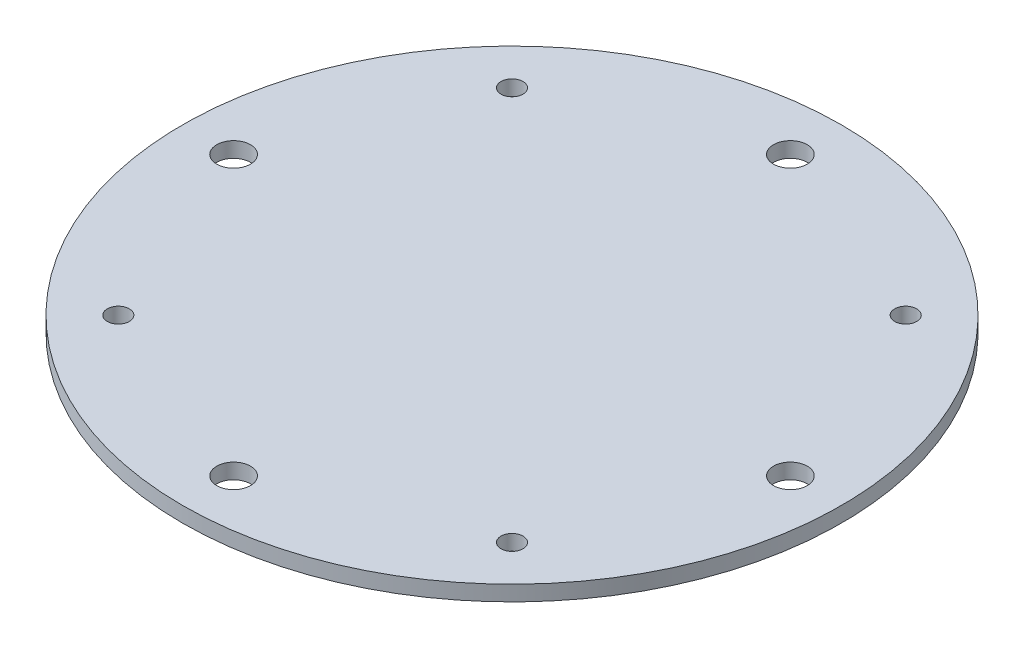
SolidWorks part; units mm, degrees
ref_plane "Front Plane" through (0, 0, 0) normal (0, 0, 1) x (1, 0, 0)
ref_plane "Top Plane" through (0, 0, 0) normal (0, 1, 0) x (1, 0, 0)
ref_plane "Right Plane" through (0, 0, 0) normal (1, 0, 0) x (0, 0, -1)
sketch "Sketch1" plane through (0, 0, 0) normal (0, 1, 0) x (1, 0, 0)
  circle A0 centre (0, 0) radius 64.4
  dimension "Diameter" = 128.8
extrude "Boss-Extrude1" add sketch "Sketch1" along normal mid plane 3
hole_wizard "M6 Clearance Hole1" positions "Sketch8" profile "Sketch9" hole size "M6" standard "ANSI Metric" end condition up to next
sketch "Sketch8" plane through (0, 1.5, 0) normal (0, 1, 0) x (1, 0, 0)
  line L0 (0, 0) -> (54.4, 0) construction
  point P0 (54.4, 0)
  dimension "ThreadedHoleDistance" = 54.4
sketch "Sketch9" plane through (54.4, 1.5, 0) normal (1, 0, 0) x (0, 0, 1)
  line L0 (0, 0) -> (0, 3)
  line L1 (0, 3) -> (3.3, 3)
  line L2 (3.3, 3) -> (3.3, 0)
  line L5 (3.3, 0) -> (0, 0)
  line L11 (0, -6.35) -> (0, 107.95) construction
  dimension "Thru Hole Dia." = 6.6
  dimension "Thru Hole Depth" = 3
pattern_circular "CirPattern2" count 4 over 360 about axis through (0, 1.5, 0) along (0, -1, 0) of "M6 Clearance Hole1" reverse direction yes
sketch "Sketch5" plane through (0, 1.5, 0) normal (0, 1, 0) x (1, 0, 0)
  line L0 (0, 0) -> (64.4, 0) construction
  line L2 (0, 0) -> (38.4666, 38.4666) construction
  circle A0 centre (0, 0) radius 64.4 construction
  dimension "D1" = 45
  dimension " NoseShellHoleRadius" = 54.4
hole_wizard "M4 Clearance Hole1" positions "Sketch6" profile "Sketch7" hole size "M4" standard "ANSI Metric" end condition up to next
sketch "Sketch6" plane through (0, 1.5, 0) normal (0, 1, 0) x (1, 0, 0)
  point P0 (38.4666, 38.4666)
sketch "Sketch7" plane through (38.4666, 1.5, -38.4666) normal (1, 0, 0) x (0, 0, 1)
  line L0 (0, 0) -> (0, 3)
  line L1 (0, 3) -> (2.15, 3)
  line L2 (2.15, 3) -> (2.15, 0)
  line L5 (2.15, 0) -> (0, 0)
  line L11 (0, -6.35) -> (0, 107.95) construction
  dimension "Thru Hole Dia." = 4.3
  dimension "Thru Hole Depth" = 3
pattern_circular "CirPattern1" count 4 over 360 about axis through (0, 1.5, 0) along (0, -1, 0) of "M4 Clearance Hole1" reverse direction yes
